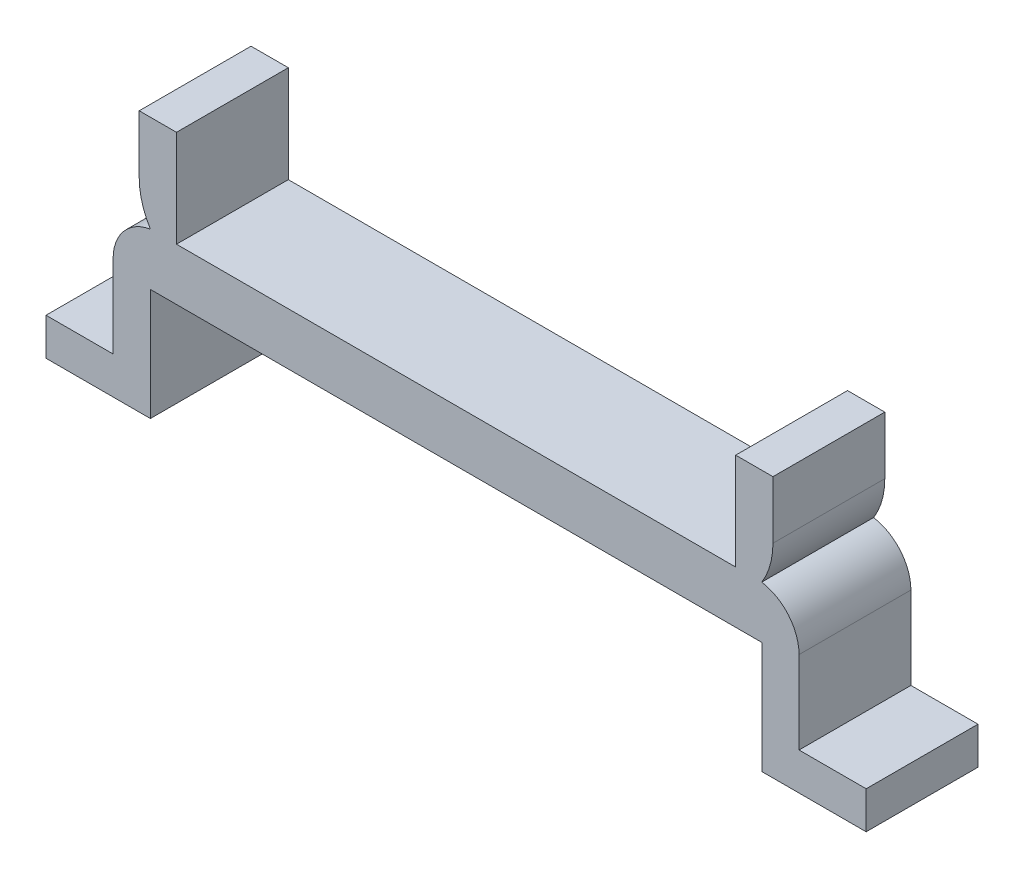
SolidWorks part; units mm, degrees
ref_plane "Front Plane" through (0, 0, 0) normal (0, 0, 1) x (1, 0, 0)
ref_plane "Top Plane" through (0, 0, 0) normal (0, 1, 0) x (1, 0, 0)
ref_plane "Right Plane" through (0, 0, 0) normal (1, 0, 0) x (0, 0, -1)
sketch "Sketch1" plane through (0, 0, 0) normal (0, 1, 0) x (1, 0, 0)
  line L1 (-41, 7.5) -> (41, 7.5)
  line L2 (-41, 7.5) -> (-41, -7.5)
  line L3 (-41, -7.5) -> (41, -7.5)
  line L4 (41, 7.5) -> (41, -7.5)
  point P4 (0, -7.5)
  point P6 (41, 0)
  dimension "D1" = 15
  dimension "D2" = 82
extrude "Boss-Extrude1" add sketch "Sketch1" along normal blind 7
sketch "Sketch3" plane through (0, 7, 0) normal (0, 1, 0) x (1, 0, 0)
  line L0 (41, 7.5) -> (-41, 7.5) construction
  line L1 (-42.5, 7.5) -> (-37.5, 7.5)
  line L2 (-42.5, 7.5) -> (-42.5, -7.5)
  line L3 (-42.5, -7.5) -> (-37.5, -7.5)
  line L4 (-37.5, 7.5) -> (-37.5, -7.5)
  line L5 (-41, -7.5) -> (41, -7.5) construction
  line L7 (37.5, 7.5) -> (42.5, 7.5)
  line L8 (37.5, 7.5) -> (37.5, -7.5)
  line L9 (37.5, -7.5) -> (42.5, -7.5)
  line L10 (42.5, 7.5) -> (42.5, -7.5)
  dimension "D1" = 75
  dimension "D2" = 5
  dimension "D3" = 37.5
extrude "Boss-Extrude2" add sketch "Sketch3" along normal blind 13
fillet "Fillet1" radius 10 2 edges at (42.5, 7, 0) (-42.5, 7, 0)
sketch "Sketch4" plane through (0, 0, -7.5) normal (0, 0, -1) x (-1, 0, 0)
  line L0 (0, 8.25) -> (0, -8.25) construction
  line L1 (-41, 7) -> (-46, 7)
  line L2 (-41, 7) -> (-41, -15)
  line L3 (-41, -15) -> (-46, -15)
  line L4 (-46, 7) -> (-46, -15)
  line L5 (41, -15) -> (46, -15)
  line L6 (46, 7) -> (46, -15)
  line L7 (41, 7) -> (46, 7)
  line L8 (41, 7) -> (41, -15)
  dimension "D1" = 15
  dimension "D2" = 5
extrude "Boss-Extrude3" add sketch "Sketch4" against normal up to surface (15 mm away) up to face at (0, 11.0272, 7.5)
fillet "Fillet2" radius 6 2 edges at (46, 7, 0) (-46, 7, 0)
sketch "Sketch5" plane through (-46, 0, 0) normal (-1, 0, 0) x (0, 0, 1)
  line L0 (7.5, 1.0839) -> (7.5, -15) construction
  line L1 (-7.5, -15) -> (7.5, -15)
  line L2 (-7.5, -15) -> (-7.5, -10)
  line L3 (-7.5, -10) -> (7.5, -10)
  line L4 (7.5, -15) -> (7.5, -10)
  dimension "D1" = 5
extrude "Boss-Extrude4" add sketch "Sketch5" along normal blind 9
mirror "Mirror1" about plane through (0, 0, 0) normal (1, 0, 0) of "Boss-Extrude4"
